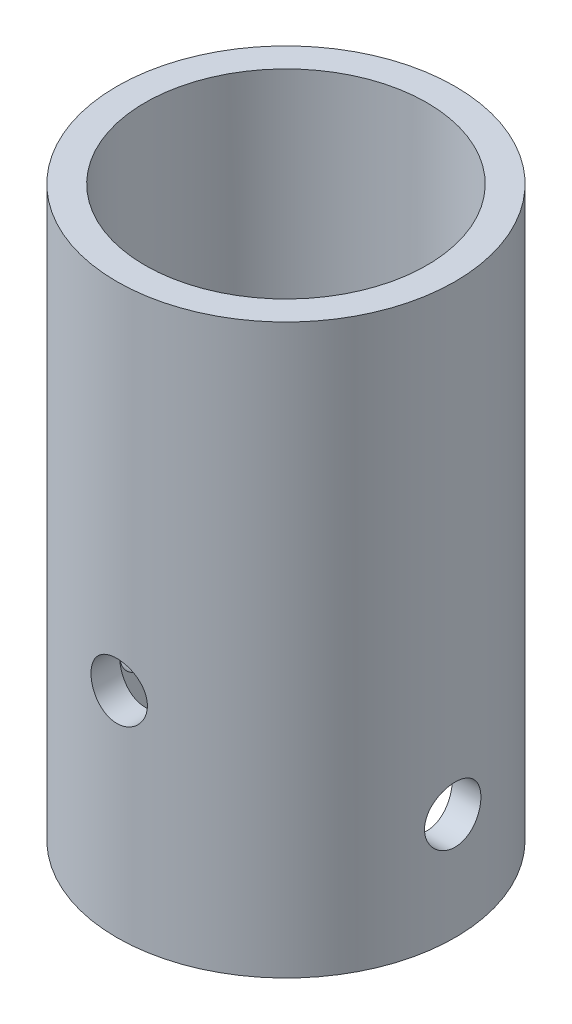
SolidWorks part; units mm, degrees
material "AISI 1020"
ref_plane "Front Plane" through (0, 0, 0) normal (0, 0, 1) x (1, 0, 0)
ref_plane "Top Plane" through (0, 0, 0) normal (0, 1, 0) x (1, 0, 0)
ref_plane "Right Plane" through (0, 0, 0) normal (1, 0, 0) x (0, 0, -1)
sketch "Sketch1" plane through (0, 0, 0) normal (0, 1, 0) x (1, 0, 0)
  circle A0 centre (0, 0) radius 7.9375
  circle A1 centre (0, 0) radius 9.525
  dimension "D1" = 15.875
  dimension "D2" = 19.05
extrude "Boss-Extrude1" add sketch "Sketch1" along normal blind 20 and the other way blind 20
sketch "Sketch2" plane through (0, 0, 0) normal (0, 1, 0) x (1, 0, 0)
  circle A0 centre (0, 0) radius 7.9375
  circle A1 centre (0, 0) radius 7.1781
extrude "Boss-Extrude2" add sketch "Sketch2" along normal blind 0.5 and the other way blind 0.5
sketch "Sketch3" plane through (0, 0, 0) normal (1, 0, 0) x (0, 0, -1)
  line L0 (0, -20) -> (0, -14) construction
  line L1 (-9.525, -20) -> (9.525, -20) construction
  circle A0 centre (0, -14) radius 1.5875
  dimension "D1" = 3.175
extrude "Cut-Extrude1" cut sketch "Sketch3" against normal blind 10 and the other way blind 10
sketch "Sketch4" plane through (0, 0, 0) normal (0, 0, 1) x (1, 0, 0)
  line L0 (-9.525, -12.4125) -> (-9.525, -15.5875) construction
  line L1 (-9.525, -14) -> (0, -14) construction
  line L2 (0, -14) -> (0, -7.965) construction
  circle A0 centre (0, -7.965) radius 1.5875
  dimension "D1" = 3.175
extrude "Cut-Extrude2" cut sketch "Sketch4" against normal blind 10 and the other way blind 10
sketch "Sketch5" plane through (0, 20, 0) normal (0, 1, 0) x (1, 0, 0)
  line L1 (13.7323, 12.1333) -> (-13.7323, 12.1333)
  line L2 (13.7323, 12.1333) -> (13.7323, -12.1333)
  line L3 (13.7323, -12.1333) -> (-13.7323, -12.1333)
  line L4 (-13.7323, 12.1333) -> (-13.7323, -12.1333)
  line L5 (13.7323, 12.1333) -> (-13.7323, -12.1333) construction
  line L6 (13.7323, -12.1333) -> (-13.7323, 12.1333) construction
  point P0 (0, 0)
extrude "Cut-Extrude3" cut sketch "Sketch5" against normal blind 8
